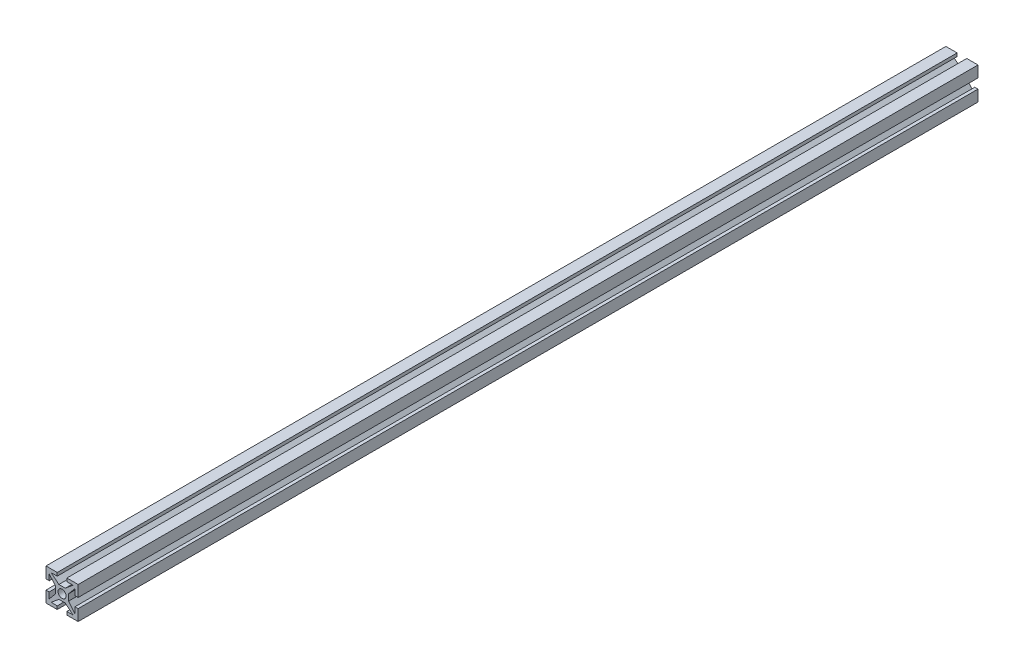
SolidWorks part; units mm, degrees
ref_plane "Front Plane" through (0, 0, 0) normal (0, 0, 1) x (1, 0, 0)
ref_plane "Top Plane" through (0, 0, 0) normal (0, 1, 0) x (1, 0, 0)
ref_plane "Right Plane" through (0, 0, 0) normal (1, 0, 0) x (0, 0, -1)
sketch "Esquisse2" plane through (0, 0, 0) normal (0, 0, 1) x (1, 0, 0)
  line L0 (-1, -2) -> (1, -2)
  line L1 (1, -2) -> (3.3835, -4)
  line L2 (3.3835, -4) -> (1.5, -4)
  line L3 (1.5, -4) -> (1.5, -5)
  line L4 (1.5, -5) -> (5, -5)
  line L5 (-1, -2) -> (-3.3835, -4)
  line L6 (-3.3835, -4) -> (-1.5, -4)
  line L7 (-1.5, -4) -> (-1.5, -5)
  line L8 (-1.5, -5) -> (-5, -5)
  line L9 (-5, -5) -> (-5, -1.5)
  line L10 (-5, -1.5) -> (-4, -1.5)
  line L11 (-4, -1.5) -> (-4, -3.3835)
  line L12 (-4, -3.3835) -> (-2, -1)
  line L13 (-2, -1) -> (-2, 1)
  line L14 (-2, 1) -> (-4, 3.3835)
  line L15 (-4, 3.3835) -> (-4, 1.5)
  line L16 (-4, 1.5) -> (-5, 1.5)
  line L17 (-5, 1.5) -> (-5, 5)
  line L18 (-5, 5) -> (-1.5, 5)
  line L19 (-1.5, 5) -> (-1.5, 4)
  line L20 (-1.5, 4) -> (-3.3835, 4)
  line L21 (-3.3835, 4) -> (-1, 2)
  line L22 (-1, 2) -> (1, 2)
  line L23 (1, 2) -> (3.3835, 4)
  line L24 (3.3835, 4) -> (1.5, 4)
  line L25 (1.5, 4) -> (1.5, 5)
  line L26 (1.5, 5) -> (5, 5)
  line L27 (5, 5) -> (5, 1.5)
  line L28 (5, 1.5) -> (4, 1.5)
  line L29 (4, 1.5) -> (4, 3.3835)
  line L30 (4, 3.3835) -> (2, 1)
  line L31 (2, -1) -> (2, 1)
  line L32 (2, -1) -> (4, -3.3835)
  line L33 (4, -3.3835) -> (4, -1.5)
  line L34 (4, -1.5) -> (5, -1.5)
  line L35 (5, -1.5) -> (5, -5)
  circle A0 centre (0, 0) radius 1.25
  point P4 (0, -2)
  point P34 (0, 2)
  point P40 (2, 0)
  dimension "D4" = 2.5
  dimension "D1" = 2
  dimension "D2" = 3.5
  dimension "D3" = 1
  dimension "D5" = 10
  dimension "D6" = 10
  dimension "D7" = 140
  dimension "D8" = 4
  dimension "D9" = 4
  dimension "D10" = 3.5
  dimension "D11" = 3
extrude "Main Extrusion" add sketch "Esquisse2" along normal blind 280
